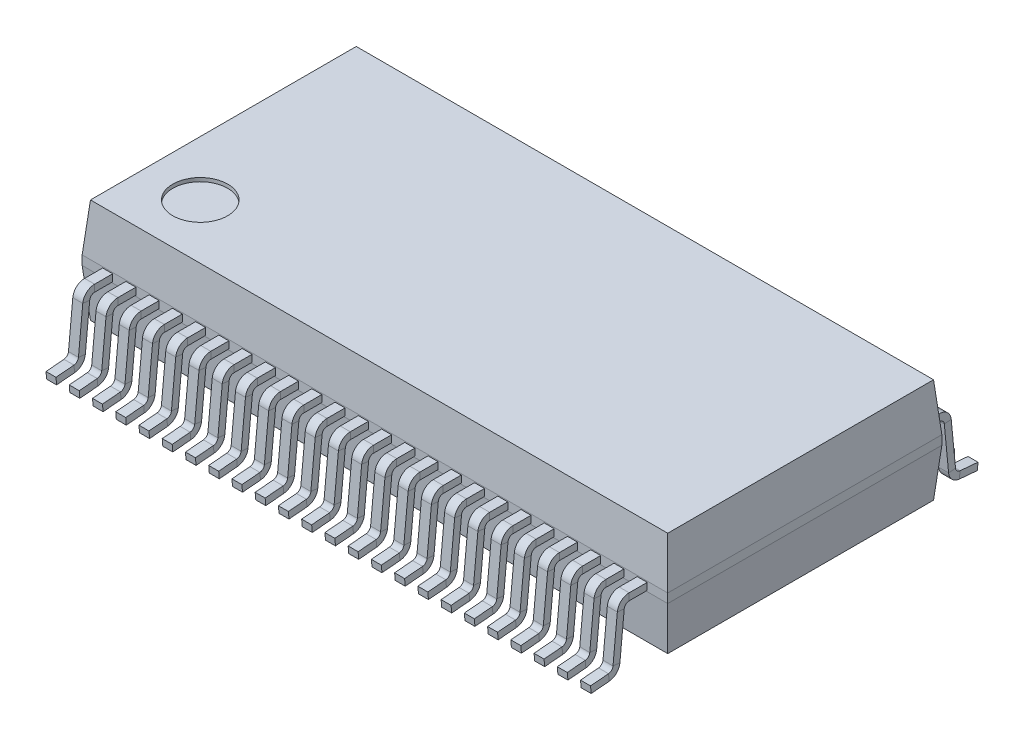
SolidWorks part; units mm, degrees
ref_plane "Front Plane" through (0, 0, 0) normal (0, 0, 1) x (1, 0, 0)
ref_plane "Top Plane" through (0, 0, 0) normal (0, 1, 0) x (1, 0, 0)
ref_plane "Right Plane" through (0, 0, 0) normal (1, 0, 0) x (0, 0, -1)
sketch "Sketch1" plane through (0, 0, 0) normal (0, 1, 0) x (1, 0, 0)
  line L1 (0, 0) -> (16, 0)
  line L2 (0, 0) -> (0, 7.49)
  line L3 (0, 7.49) -> (16, 7.49)
  line L4 (16, 0) -> (16, 7.49)
  dimension "D1" = 7.49
  dimension "D2" = 16
extrude "Boss-Extrude1" add sketch "Sketch1" along normal blind 0.25
sketch "Sketch2" plane through (0, 0.25, 0) normal (0, 1, 0) x (1, 0, 0)
  line L1 (0, 0) -> (16, 0)
  line L2 (0, 0) -> (0, 7.49)
  line L3 (0, 7.49) -> (16, 7.49)
  line L4 (16, 0) -> (16, 7.49)
extrude "Boss-Extrude2" add sketch "Sketch2" along normal blind 1.3 draft 5
sketch "Sketch3" plane through (0, 0, 0) normal (0, -1, 0) x (1, 0, 0)
  line L1 (0, 0) -> (16, 0)
  line L2 (0, 0) -> (0, -7.49)
  line L3 (0, -7.49) -> (16, -7.49)
  line L4 (16, 0) -> (16, -7.49)
extrude "Boss-Extrude3" add sketch "Sketch3" along normal blind 1.3 draft 5
sketch "Sketch4" plane through (0, 0, 0) normal (0, 0, 1) x (1, 0, 0)
  line L0 (0, 0.125) -> (0.6975, 0.125) construction
  line L1 (0.561, 0.03) -> (0.834, 0.03)
  line L2 (0.561, 0.03) -> (0.561, 0.22)
  line L3 (0.561, 0.22) -> (0.834, 0.22)
  line L4 (0.834, 0.03) -> (0.834, 0.22)
  line L5 (0.561, 0.03) -> (0.834, 0.22) construction
  line L6 (0.561, 0.22) -> (0.834, 0.03) construction
  line L7 (0, 0.25) -> (0, 0) construction
  point P0 (0.6975, 0.125)
  dimension "D1" = 0.6975
  dimension "D2" = 0.19
  dimension "D3" = 0.273
sketch "Sketch5" plane through (0, 0, 0) normal (1, 0, 0) x (0, 0, -1)
  line L0 (0, 0.125) -> (-0.4931, 0.125)
  line L1 (0, 0.25) -> (0, 0) construction
  line L2 (-0.722, -0.0828) -> (-0.84, -1.3)
  line L3 (-1.0488, -1.5069) -> (-1.54, -1.55)
  line L4 (-1.54, -1.55) -> (0, -1.55) construction
  line L5 (0, 0.125) -> (0, -1.55) construction
  line L8 (-0.84, -1.3) -> (0, -1.3) construction
  line L9 (0.1137, -1.3) -> (7.3763, -1.3) construction
  arc A0 (-0.4931, 0.125) -> (-0.722, -0.0828) centre (-0.4931, -0.105) ccw
  arc A1 (-0.84, -1.3) -> (-1.0488, -1.5069) centre (-1.0689, -1.2778) cw
  dimension "D2" = 0.23
  dimension "D1" = 1.54
  dimension "D3" = 0.25
  dimension "D4" = 0.7
sweep "Sweep1" add profiles "Sketch4" path "Sketch5"
pattern_linear "LPattern1" count 24 spacing 0.635 along (1, 0, 0) of "Sweep1"
ref_plane "Plane1" through (0, 0, -3.745) normal (0, 0, 1) x (1, 0, 0)
mirror "Mirror1" about plane through (0, 0, -3.745) normal (0, 0, 1) of "LPattern1"
sketch "Sketch6" plane through (0, 1.55, 0) normal (0, 1, 0) x (1, 0, 0)
  line L0 (1.6137, 1.6137) -> (1.6137, 0.1137) construction
  line L1 (0.1137, 0.1137) -> (15.8863, 0.1137) construction
  line L2 (1.6137, 1.6137) -> (0.1137, 1.6137) construction
  line L3 (0.1137, 7.3763) -> (0.1137, 0.1137) construction
  circle A0 centre (1.6137, 1.6137) radius 0.75
  dimension "D2" = 1.5
  dimension "D1" = 1.5
extrude "Cut-Extrude1" cut sketch "Sketch6" against normal blind 0.1
